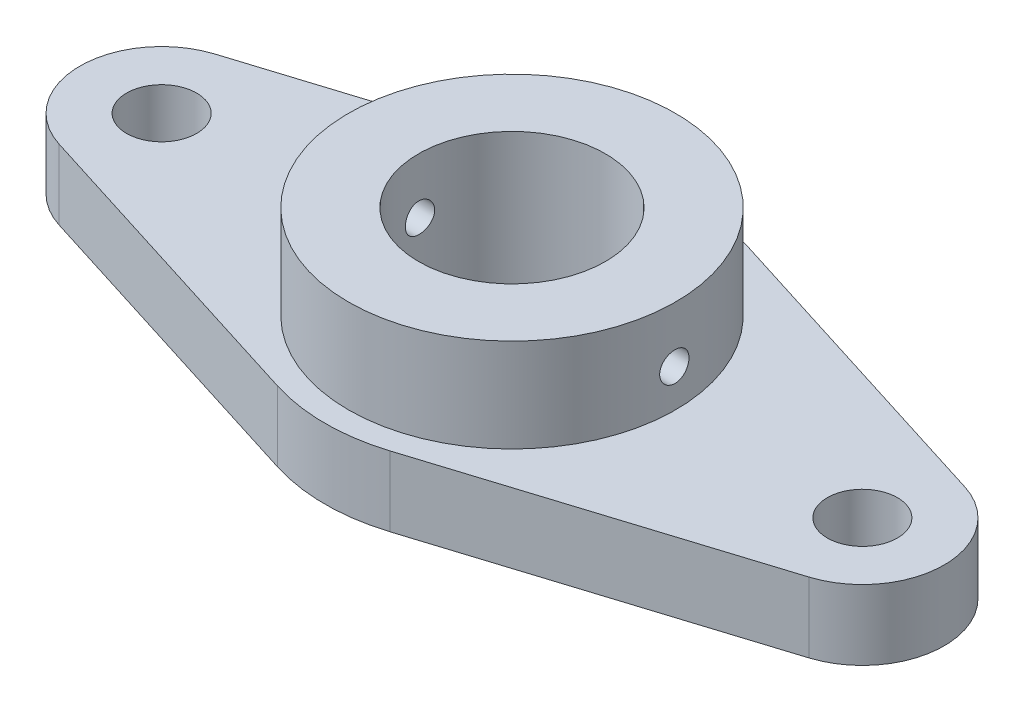
SolidWorks part; units mm, degrees
material "ABS"
ref_plane "前视基准面" through (0, 0, 0) normal (0, 0, 1) x (1, 0, 0)
ref_plane "上视基准面" through (0, 0, 0) normal (0, 1, 0) x (1, 0, 0)
ref_plane "右视基准面" through (0, 0, 0) normal (1, 0, 0) x (0, 0, -1)
sketch "草图1" plane through (0, 0, 0) normal (0, 1, 0) x (1, 0, 0)
  line L0 (-16.05, 3.3388) -> (-2.4, 7.6315)
  line L1 (-16.05, -3.3388) -> (-2.4, -7.6315)
  line L2 (2.4, 7.6315) -> (16.05, 3.3388)
  line L3 (2.4, -7.6315) -> (16.05, -3.3388)
  circle A0 centre (0, 0) radius 4
  arc A1 (-2.4, -7.6315) -> (2.4, -7.6315) centre (0, 0) ccw
  circle A2 centre (15, 0) radius 1.5
  circle A3 centre (-15, 0) radius 1.5
  arc A4 (-16.05, 3.3388) -> (-16.05, -3.3388) centre (-15, 0) ccw
  arc A5 (16.05, -3.3388) -> (16.05, 3.3388) centre (15, 0) ccw
  arc A6 (2.4, 7.6315) -> (-2.4, 7.6315) centre (0, 0) ccw
  circle A7 centre (0, 0) radius 7
  dimension "D1" = 8
  dimension "D2" = 16
  dimension "D3" = 3
  dimension "D4" = 3
  dimension "D5" = 15
  dimension "D6" = 15
  dimension "D7" = 7
  dimension "D8" = 7
  dimension "D9" = 14
extrude "凸台-拉伸1" add sketch "草图1" along normal blind 3 contours L2 A6 L0 A4 L1 A1 L3 A5 A7 A2 A3 region at (-9.1041, 0, -5.1006)
extrude "凸台-拉伸2" add sketch "草图1<3>" along normal blind 7 contours A7 A0 region at (-6.802, 0, 0)
sketch "草图1<3>" plane through (0, 0, 0) normal (0, 1, 0) x (1, 0, 0) same geometry as "草图1"
hole_wizard "M1.6 螺纹孔1" positions "3D草图1" profile "草图3" tap size "M1.6" standard "GB" end condition through all
sketch3d "3D草图1"
  point P0 (7, 4.6193, 0.0231)
sketch "草图3" plane through (7, 4.6193, 0.0231) normal (0, 1, 0) x (0.0033, 0, -1)
  line L0 (0, 0) -> (0, 25.5264)
  line L1 (0, 25.5264) -> (0.625, 25.5264)
  line L2 (0.625, 25.5264) -> (0.625, 0)
  line L5 (0.625, 0) -> (0, 0)
  line L11 (0, -6.35) -> (0, 107.95) construction
  dimension "通孔螺纹孔钻头直径" = 1.25
  dimension "通孔螺纹孔钻头深度" = 25.5264
cosmetic thread "孔螺蚊线1" parameters "D2"=1.6
